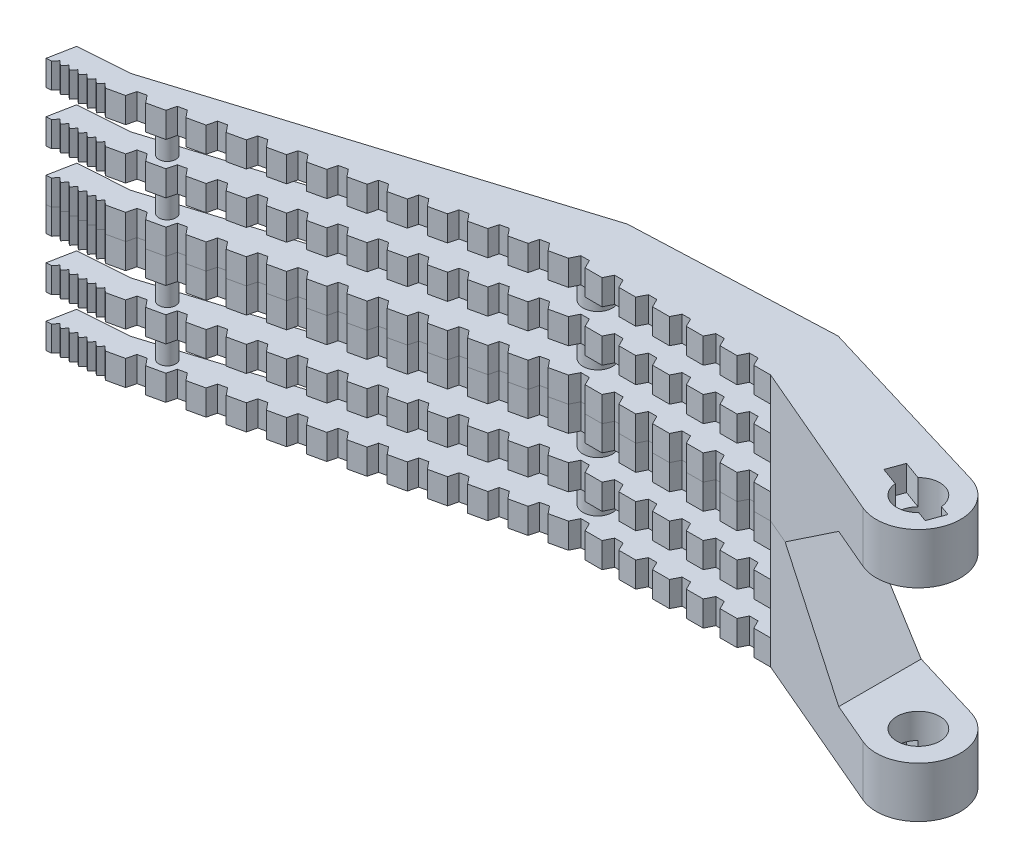
SolidWorks part; units mm, degrees
ref_plane "前视基准面" through (0, 0, 0) normal (0, 0, 1) x (1, 0, 0)
ref_plane "上视基准面" through (0, 0, 0) normal (0, 1, 0) x (1, 0, 0)
ref_plane "右视基准面" through (0, 0, 0) normal (1, 0, 0) x (0, 0, -1)
other "Configuration Table"
ref_axis "基准轴1" through (0, -20.495, 0) along (0, 1, 0)
sketch "草图1" plane through (0, 0, 0) normal (0, 1, 0) x (1, 0, 0)
  line L10 (0, 0) -> (0, -6.4) construction
  line L11 (0, -6.4) -> (-90, -6.4) construction
  line L27 (-1.9651, -4.5977) -> (-21.0954, 3.5788)
  line L29 (-45.0954, 3.5788) -> (-90, -6.4) construction
  line L31 (-90, -3.3924) -> (-45.0954, 10.5788)
  line L32 (-45.0954, 10.5788) -> (-21.0954, 11.5788)
  line L33 (-21.0954, 11.5788) -> (1.4426, 4.7874)
  line L34 (-87.7765, -4.8815) -> (-86.8003, -4.6646)
  line L35 (-86.8003, -4.6646) -> (-86.0953, -5.5323)
  line L36 (-87.7765, -4.8815) -> (-88.0476, -5.9661)
  line L37 (-87.2884, -4.773) -> (-87.0714, -5.7492) construction
  line L38 (-86.0953, -5.5323) -> (-84.1429, -5.0984)
  line L39 (-88.0476, -5.9661) -> (-90, -6.4)
  line L40 (-83.8717, -4.0138) -> (-84.1429, -5.0984)
  line L41 (-83.8717, -4.0138) -> (-82.8955, -3.7968)
  line L42 (-82.8955, -3.7968) -> (-82.1905, -4.6646)
  line L43 (-82.1905, -4.6646) -> (-80.2381, -4.2307)
  line L44 (-79.967, -3.146) -> (-80.2381, -4.2307)
  line L45 (-79.967, -3.146) -> (-78.9908, -2.9291)
  line L46 (-78.9908, -2.9291) -> (-78.2858, -3.7968)
  line L47 (-78.2858, -3.7968) -> (-76.3334, -3.363)
  line L48 (-76.0622, -2.2783) -> (-76.3334, -3.363)
  line L49 (-76.0622, -2.2783) -> (-75.086, -2.0614)
  line L50 (-75.086, -2.0614) -> (-74.381, -2.9291)
  line L51 (-74.381, -2.9291) -> (-72.4286, -2.4953)
  line L52 (-72.1575, -1.4106) -> (-72.4286, -2.4953)
  line L53 (-72.1575, -1.4106) -> (-71.1813, -1.1937)
  line L54 (-71.1813, -1.1937) -> (-70.4763, -2.0614)
  line L55 (-70.4763, -2.0614) -> (-68.5239, -1.6275)
  line L56 (-68.2527, -0.5429) -> (-68.5239, -1.6275)
  line L57 (-68.2527, -0.5429) -> (-67.2765, -0.3259)
  line L58 (-67.2765, -0.3259) -> (-66.5715, -1.1937)
  line L59 (-66.5715, -1.1937) -> (-64.6191, -0.7598)
  line L60 (-64.348, 0.3248) -> (-64.6191, -0.7598)
  line L61 (-64.348, 0.3248) -> (-63.3718, 0.5418)
  line L62 (-63.3718, 0.5418) -> (-62.6668, -0.3259)
  line L63 (-62.6668, -0.3259) -> (-60.7144, 0.1079)
  line L64 (-60.4432, 1.1926) -> (-60.7144, 0.1079)
  line L65 (-60.4432, 1.1926) -> (-59.467, 1.4095)
  line L66 (-59.467, 1.4095) -> (-58.762, 0.5418)
  line L67 (-58.762, 0.5418) -> (-56.8096, 0.9756)
  line L68 (-56.5385, 2.0603) -> (-56.8096, 0.9756)
  line L69 (-56.5385, 2.0603) -> (-55.5623, 2.2772)
  line L70 (-55.5623, 2.2772) -> (-54.8573, 1.4095)
  line L71 (-54.8573, 1.4095) -> (-52.9049, 1.8434)
  line L72 (-52.6337, 2.928) -> (-52.9049, 1.8434)
  line L73 (-52.6337, 2.928) -> (-51.6575, 3.1449)
  line L74 (-51.6575, 3.1449) -> (-50.9525, 2.2772)
  line L75 (-50.9525, 2.2772) -> (-49.0001, 2.7111)
  line L76 (-48.729, 3.7957) -> (-49.0001, 2.7111)
  line L77 (-48.729, 3.7957) -> (-47.7528, 4.0127)
  line L78 (-47.7528, 4.0127) -> (-47.0478, 3.1449)
  line L79 (-47.0478, 3.1449) -> (-45.0954, 3.5788)
  line L80 (-43.0954, 3.5788) -> (-41.0954, 3.5788)
  line L81 (-45.0954, 3.5788) -> (-44.5954, 4.5788)
  line L82 (-44.5954, 4.5788) -> (-43.5954, 4.5788)
  line L83 (-43.5954, 4.5788) -> (-43.0954, 3.5788)
  line L84 (-45.0954, 3.5788) -> (-43.0954, 3.5788) construction
  line L85 (-23.3489, 3.5788) -> (-29.0874, 3.5788) construction
  line L86 (-41.0954, 3.5788) -> (-40.5954, 4.5788)
  line L87 (-40.5954, 4.5788) -> (-39.5954, 4.5788)
  line L88 (-39.5954, 4.5788) -> (-39.0954, 3.5788)
  line L89 (-39.0954, 3.5788) -> (-37.0954, 3.5788)
  line L90 (-41.0954, 3.5788) -> (-39.0954, 3.5788) construction
  line L91 (-37.0954, 3.5788) -> (-36.5954, 4.5788)
  line L92 (-36.5954, 4.5788) -> (-35.5954, 4.5788)
  line L93 (-35.5954, 4.5788) -> (-35.0954, 3.5788)
  line L94 (-35.0954, 3.5788) -> (-33.0954, 3.5788)
  line L95 (-37.0954, 3.5788) -> (-35.0954, 3.5788) construction
  line L96 (-33.0954, 3.5788) -> (-32.5954, 4.5788)
  line L97 (-32.5954, 4.5788) -> (-31.5954, 4.5788)
  line L98 (-31.5954, 4.5788) -> (-31.0954, 3.5788)
  line L99 (-31.0954, 3.5788) -> (-29.0954, 3.5788)
  line L100 (-33.0954, 3.5788) -> (-31.0954, 3.5788) construction
  line L101 (-29.0954, 3.5788) -> (-28.5954, 4.5788)
  line L102 (-28.5954, 4.5788) -> (-27.5954, 4.5788)
  line L103 (-27.5954, 4.5788) -> (-27.0954, 3.5788)
  line L104 (-27.0954, 3.5788) -> (-25.0954, 3.5788)
  line L105 (-29.0954, 3.5788) -> (-27.0954, 3.5788) construction
  line L106 (-25.0954, 3.5788) -> (-24.5954, 4.5788)
  line L107 (-24.5954, 4.5788) -> (-23.5954, 4.5788)
  line L108 (-23.5954, 4.5788) -> (-23.0954, 3.5788)
  line L109 (-23.0954, 3.5788) -> (-21.0954, 3.5788)
  line L110 (-25.0954, 3.5788) -> (-23.0954, 3.5788) construction
  line L111 (-21.0954, 11.5788) -> (-21.0954, 3.5788) construction
  line L112 (-90, -6.4) -> (0, 0) construction
  line L114 (-96.5834, -6.8682) -> (-95.9943, -3.8187)
  line L115 (-95.9943, -3.8187) -> (-90, -3.3924)
  line L116 (-96.5834, -6.8682) -> (-95.9849, -6.8256)
  line L117 (-91.5317, -6.0077) -> (-91.995, -6.5419)
  line L118 (-90.9975, -6.4709) -> (-91.5317, -6.0077)
  line L119 (-92.5292, -6.0786) -> (-92.9924, -6.6128)
  line L120 (-96.5834, -6.8682) -> (-90, -6.4) construction
  line L121 (-90, -6.4) -> (-90.5342, -5.9367)
  line L122 (-90.5342, -5.9367) -> (-90.9975, -6.4709)
  line L123 (-90.5342, -5.9367) -> (-90.4933, -6.5115) construction
  line L124 (-91.995, -6.5419) -> (-92.5292, -6.0786)
  line L125 (-93.5267, -6.1495) -> (-93.9899, -6.6837)
  line L126 (-92.9924, -6.6128) -> (-93.5267, -6.1495)
  line L127 (-94.5241, -6.2205) -> (-94.9874, -6.7547)
  line L128 (-93.9899, -6.6837) -> (-94.5241, -6.2205)
  line L129 (-95.5216, -6.2914) -> (-95.9849, -6.8256)
  line L130 (-94.9874, -6.7547) -> (-95.5216, -6.2914)
  arc A0 (1.4426, 4.7874) -> (-1.9651, -4.5977) centre (0, 0) cw
  point P38 (-44.0954, 4.5788)
  point P43 (-44.0954, 3.5788)
  point P72 (-96.9824, -6.8965)
  point P77 (0, 0)
  point P82 (-89.0427, -2.2783)
  point P87 (-95.928, -6.8256)
  point P95 (-89.3704, -3.363)
  point P98 (0, 0)
  dimension "D4" = 7
  dimension "D3" = 5
  dimension "D1" = 6.4
  dimension "D5" = 6
  dimension "D6" = 2
  dimension "D7" = 8
  dimension "D8" = 2
  dimension "D9" = 0.6
  dimension "D10" = 1
  dimension "D11" = 1
  dimension "D12" = 1
  dimension "D13" = 2
  dimension "D14" = 2
  dimension "D15" = 2
  dimension "D17" = 1
  dimension "D18" = 1
  dimension "D19" = 6
  dimension "D20" = 75
  dimension "D21" = 3
  dimension "D16" = 11
extrude "凸台-拉伸2" add sketch "草图1" along normal blind 15 and the other way blind 15
sketch "草图10" plane through (0, 0, 0) normal (0, 0, 1) x (1, 0, 0)
  line L0 (5, 9) -> (-7, 9)
  line L1 (5, -15) -> (5, 15) construction
  line L4 (55, 0) -> (-55, 0) construction
  line L8 (5, 15) -> (-1.9651, 15) construction
  line L12 (-18.0954, 0) -> (19.8896, 0) construction
  line L14 (-18.0954, 0) -> (-7, 9)
  line L15 (5, 9) -> (5, -9)
  line L16 (5, -15) -> (5, 15) construction
  line L17 (-18.0954, 0) -> (-7, -9)
  line L18 (5, -9) -> (-7, -9)
  line L19 (-21.0954, -15) -> (-21.0954, 15) construction
  point P18 (5, 0)
  point P26 (5, 0)
  dimension "D1" = 6
  dimension "D2" = 3
  dimension "D3" = 12
extrude "切除-拉伸7" cut sketch "草图10" against normal through all and the other way through all
sketch "草图3" plane through (0, 0, 0) normal (0, 0, 1) x (1, 0, 0)
  line L0 (-21.0954, 15) -> (-1.9651, 15) construction
  line L1 (-121.0954, 12) -> (-21.0954, 12)
  line L2 (-121.0954, 12) -> (-121.0954, 9)
  line L3 (-121.0954, 9) -> (-21.0954, 9)
  line L4 (-21.0954, 12) -> (-21.0954, 9)
  line L5 (-21.0954, 38.654) -> (-21.0954, -13.8848) construction
  line L8 (-21.0954, -15) -> (-21.0954, 15) construction
  line L10 (-121.0954, 6) -> (-21.0954, 6)
  line L11 (-121.0954, 6) -> (-121.0954, 3)
  line L12 (-121.0954, 3) -> (-21.0954, 3)
  line L13 (-21.0954, 6) -> (-21.0954, 3)
  line L14 (55, 0) -> (-55, 0) construction
  line L15 (0, 0) -> (34.3491, 0) construction
  line L16 (-21.0954, -6) -> (-21.0954, -3)
  line L17 (-121.0954, -3) -> (-21.0954, -3)
  line L18 (-121.0954, -6) -> (-121.0954, -3)
  line L19 (-121.0954, -6) -> (-21.0954, -6)
  line L20 (-21.0954, -12) -> (-21.0954, -9)
  line L21 (-121.0954, -9) -> (-21.0954, -9)
  line L22 (-121.0954, -12) -> (-121.0954, -9)
  line L23 (-121.0954, -12) -> (-21.0954, -12)
  dimension "D1" = 3
  dimension "D2" = 100
  dimension "D3" = 3
  dimension "D5" = 3
  dimension "D6" = 3
extrude "切除-拉伸8" cut sketch "草图3" against normal through all and the other way through all
sketch "草图4" plane through (0, -15, 0) normal (0, -1, 0) x (1, 0, 0)
  line L2 (-45.0954, -3.5788) -> (-45.0954, -10.5788) construction
  line L3 (-21.0954, -3.5788) -> (-21.0954, -11.5788) construction
  line L4 (-85.9456, 2.131) -> (-85.5, 3.5633) construction
  line L5 (-45.0954, -10.5788) -> (-90, 3.3924) construction
  circle A3 centre (-45.0954, -7.0788) radius 1.75
  circle A4 centre (-85.5, 3.5633) radius 1
  point P2 (0, 0)
  point P27 (-45.0954, -7.0788)
  dimension "D1" = 4.5
  dimension "D2" = 3.5
  dimension "D3" = 2
  dimension "D4" = 1.5
extrude "凸台-拉伸3" add sketch "草图4" against normal up to surface (30 mm away) up to face at (-60.3337, 15, 0.1756)
sketch "草图5" plane through (0, -15, 0) normal (0, -1, 0) x (1, 0, 0)
  circle A0 centre (0, 0) radius 2.55
  dimension "D1" = 5.1
extrude "切除-拉伸2" cut sketch "草图5" against normal through all
sketch "草图8" plane through (0, -15, 0) normal (0, -1, 0) x (1, 0, 0)
  line L0 (0, 0) -> (-4.3238, -1.57) construction
  line L1 (1.4426, -4.7874) -> (-21.0954, -11.5788) construction
  line L2 (-21.0954, -3.5788) -> (-1.9651, 4.5977) construction
  line L3 (-4.6822, -0.583) -> (-3.9654, -2.5569)
  line L7 (-4.6822, -0.583) -> (3.0255, 2.2156)
  line L8 (-3.9654, -2.5569) -> (3.7422, 0.2417)
  line L9 (0, 0) -> (3.3838, 1.2287) construction
  line L10 (3.7422, 0.2417) -> (3.0255, 2.2156)
  point P9 (-4.3238, -1.57)
  point P10 (3.3838, 1.2287)
  dimension "D1" = 4.6
  dimension "D2" = 2.1
  dimension "D3" = 3.6
extrude "切除-拉伸5" cut sketch "草图8" against normal blind 3
mirror "镜向1" about plane through (0, 0, 0) normal (0, 1, 0) of "切除-拉伸5"
sketch "草图12" plane through (0, 0, 0) normal (0, 0, 1) x (1, 0, 0)
  line L0 (-97.3133, 0) -> (15.6219, 0)
  line L1 (10.1458, 0) -> (-10.1458, 0) construction
  point P5 (-97.3133, 0)
split "分割1" trim tools "草图12" bodies to split 123 resulting bodies 124 125
